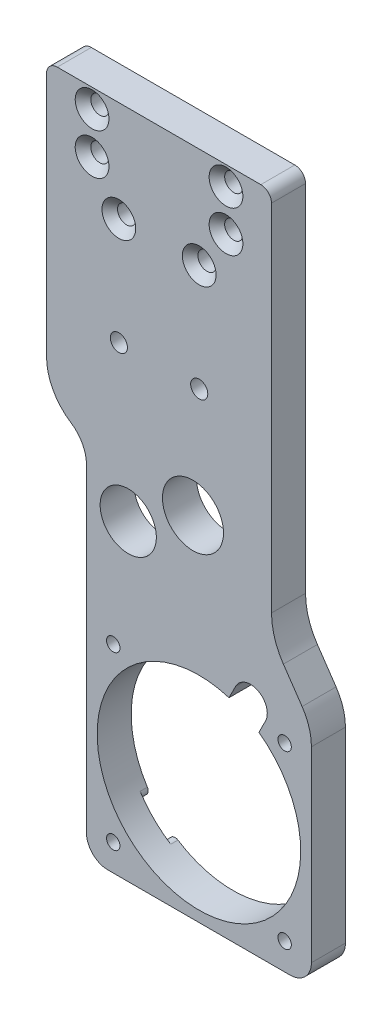
SolidWorks part; units mm, degrees
note: '?' marks a value the reader was unsure of.
ref_plane "Top Plane" through (0, 0, 0) normal (0, 0, 1) x (1, 0, 0)
ref_plane "Front Plane" through (0, 0, 0) normal (0, 1, 0) x (1, 0, 0)
ref_plane "Right Plane" through (0, 0, 0) normal (1, 0, 0) x (0, 0, -1)
sketch "HotendMountingPlateLayout" plane through (0, 0, 0) normal (0, 0, 1) x (1, 0, 0)
  line B0 (-21, 13.5) -> (21, 13.5)
  line B1 (-21, 13.5) -> (-21, -31.3716)
  line B2 (-21, -31.3716) -> (21, -31.3716)
  line B3 (21, 13.5) -> (21, -31.3716)
  line B4 (-21, 13.5) -> (21, -31.3716) construction
  line B5 (-21, -31.3716) -> (21, 13.5) construction
  line B6 (-21, -44.6284) -> (21, -44.6284)
  line B7 (-21, -44.6284) -> (-21, -31.3716)
  line B8 (-21, -31.3716) -> (21, -31.3716)
  line B9 (21, -44.6284) -> (21, -31.3716)
  line B10 (-21, -44.6284) -> (21, -31.3716) construction
  line B11 (-21, -31.3716) -> (21, -44.6284) construction
  line B12 (-13.55, -96.2852) -> (28.45, -96.2852)
  line B13 (-13.55, -96.2852) -> (-13.55, -54.2852)
  line B14 (-13.55, -54.2852) -> (28.45, -54.2852)
  line B15 (28.45, -96.2852) -> (28.45, -54.2852)
  line B16 (-13.55, -96.2852) -> (28.45, -54.2852) construction
  line B17 (-13.55, -54.2852) -> (28.45, -96.2852) construction
  circle B18 centre (-5.75, -38) radius 6.8
  circle B19 centre (0, -38) radius 6
  circle B20 centre (-5.75, -38) radius 0.875
  line B21 (-17.77, -13.5) -> (17.77, -13.5)
  line B22 (-17.77, -13.5) -> (-17.77, 13.5)
  line B23 (-17.77, 13.5) -> (17.77, 13.5)
  line B24 (17.77, -13.5) -> (17.77, 13.5)
  line B25 (-17.77, -13.5) -> (17.77, 13.5) construction
  line B26 (-17.77, 13.5) -> (17.77, -13.5) construction
  line B27 (-12.55, -95.2852) -> (27.45, -95.2852) construction
  line B28 (-12.55, -95.2852) -> (-12.55, -55.2852) construction
  line B29 (-12.55, -55.2852) -> (27.45, -55.2852) construction
  line B30 (27.45, -95.2852) -> (27.45, -55.2852) construction
  line B31 (-12.55, -95.2852) -> (27.45, -55.2852) construction
  line B32 (-12.55, -55.2852) -> (27.45, -95.2852) construction
sketch_block_instance "Block2-1"
sketch_block "Block2" parameters "D3"=12, "D4"=1.75, "D5"=13.6, "D1"=42, "D2"=42, "D6"=20, "D7"=31.7831, "D8"=17.4894, "D9"=26.5358, "D10"=6.875
sketch "Sketch43" plane through (0, 0, 0) normal (0, 0, 1) x (1, 0, 0)
  line L0 (-12.5, 17.55) -> (12.5, 17.55) construction
  line L1 (-12.5, 17.55) -> (-12.5, 25.24) construction
  line L2 (-12.5, 25.24) -> (12.5, 25.24) construction
  line L3 (12.5, 17.55) -> (12.5, 25.24) construction
  line L4 (-12.5, 17.55) -> (12.5, 25.24) construction
  line L5 (-12.5, 25.24) -> (12.5, 17.55) construction
  line L7 (-9.3246, 17.55) -> (-10.9123, 20.3)
  line L8 (-10.9123, 20.3) -> (-14.0877, 20.3)
  line L9 (-14.0877, 20.3) -> (-15.6754, 17.55)
  line L10 (-15.6754, 17.55) -> (-14.0877, 14.8)
  line L11 (-14.0877, 14.8) -> (-10.9123, 14.8)
  line L12 (-10.9123, 14.8) -> (-9.3246, 17.55)
  circle A0 centre (-12.5, 17.55) radius 2.75 construction
  point P0 (0, 21.395)
  dimension "D3" = 5.5
  dimension "D1" = 7.69
  dimension "D2" = 25
  dimension "D4" = 17.55
sketch "Sketch1" plane through (0, 0, 0) normal (0, 0, 1) x (1, 0, 0)
  line L0 (28.45, -96.2852) -> (-13.55, -96.2852)
  line L1 (-21, -41.3815) -> (-21, -54.2852)
  line L2 (-13.55, -96.2852) -> (-13.55, -54.2852)
  line L3 (-13.55, -54.2852) -> (-21, -41.3815) construction
  line L4 (-21, -41.3815) -> (-21, 28.8)
  line L5 (-21, 28.8) -> (21, 28.8)
  line L6 (21, 28.8) -> (21, -41.3815)
  line L7 (-21, -54.2852) -> (-13.55, -54.2852)
  line L8 (21, -41.3815) -> (28.45, -54.2852) construction
  line L9 (28.45, -54.2852) -> (28.45, -96.2852)
  line L10 (21, -41.3815) -> (28.45, -41.3815)
  line L11 (28.45, -41.3815) -> (28.45, -54.2852)
  line L12 (-12.5, 25.24) -> (12.5, 25.24) construction
  line L13 (21, -44.6284) -> (21, -31.3716) construction
  line L14 (-13.55, -54.2852) -> (28.45, -54.2852) construction
  line L15 (-13.55, -54.2852) -> (28.45, -96.2852) construction
  dimension "D1" = 30
  dimension "D2" = 3.56
  dimension "D3" = 42
extrude "Boss-Extrude1" add sketch "Sketch1" along normal blind 6.35
sketch "Sketch2" plane through (0, 0, 6.35) normal (0, 0, 1) x (1, 0, 0)
  circle A0 centre (7.45, -75.2852) radius 19
  dimension "D1" = 38
extrude "Cut-Extrude1" cut sketch "Sketch2" against normal through all
sketch "FanScrewLayout" plane through (0, 0, 6.35) normal (0, 0, 1) x (1, 0, 0)
  line L1 (-8.55, -91.2852) -> (23.45, -91.2852) construction
  line L2 (-8.55, -91.2852) -> (-8.55, -59.2852) construction
  line L3 (-8.55, -59.2852) -> (23.45, -59.2852) construction
  line L4 (23.45, -91.2852) -> (23.45, -59.2852) construction
  line L5 (-8.55, -91.2852) -> (23.45, -59.2852) construction
  line L6 (-8.55, -59.2852) -> (23.45, -91.2852) construction
  point P0 (7.45, -75.2852)
  dimension "D1" = 32
hole_wizard "M3x0.5 Tapped Hole1" positions "Sketch5" profile "Sketch4" tap size "M3x0.5" standard "ANSI Metric" end condition through all
sketch "Sketch5" plane through (0, 0, 6.35) normal (0, 0, 1) x (1, 0, 0)
  point P0 (-8.55, -59.2852)
  point P2 (23.45, -91.2852)
  point P5 (-8.55, -91.2852)
  point P11 (23.45, -59.2852)
sketch "Sketch4" plane through (-8.55, -59.2852, 6.35) normal (1, 0, 0) x (0, -1, 0)
  line L0 (0, 0) -> (0, 6.35)
  line L1 (0, 6.35) -> (1.25, 6.35)
  line L2 (1.25, 6.35) -> (1.25, 0)
  line L5 (1.25, 0) -> (0, 0)
  line L11 (0, -6.35) -> (0, 107.95) construction
  dimension "Thru Tap Drill Dia." = 2.5
  dimension "Thru Tap Drill Depth" = 6.35
cosmetic thread "Hole Thread3" parameters "D2"=3
cosmetic thread "Hole Thread4" [suppressed] parameters "D2"=3
cosmetic thread "Hole Thread5" [suppressed] parameters "D2"=3
cosmetic thread "Hole Thread8" parameters "D2"=3
sketch "CarriageScrewLayout" plane through (0, 0, 6.35) normal (0, 0, 1) x (1, 0, 0)
  line L1 (-7.5, -10) -> (7.5, -10) construction
  line L2 (-7.5, -10) -> (-7.5, 10) construction
  line L3 (-7.5, 10) -> (7.5, 10) construction
  line L4 (7.5, -10) -> (7.5, 10) construction
  line L5 (-7.5, -10) -> (7.5, 10) construction
  line L6 (-7.5, 10) -> (7.5, -10) construction
  point P0 (0, 0)
  dimension "D1" = 20
  dimension "D2" = 15
hole_wizard "Ø3.2 (3.2) Diameter Hole2" positions "Sketch12" profile "Sketch11" hole size "Ø3.2" standard "ANSI Metric"
sketch "Sketch12" plane through (0, 0, 6.35) normal (0, 0, 1) x (1, 0, 0)
  point P0 (7.5, -10)
  point P3 (-7.5, -10)
sketch "Sketch11" plane through (7.5, -10, 6.35) normal (1, 0, 0) x (0, -1, 0)
  line L0 (0, 0) -> (0, 9.53)
  line L1 (0, 9.53) -> (1.6, 9.53)
  line L2 (1.6, 9.53) -> (1.6, 0)
  line L5 (1.6, 0) -> (0, 0)
  line L10 (0, 9.53) -> (-1.6, 9.53) construction
  line L11 (0, -6.35) -> (0, 107.95) construction
  dimension "Hole Dia." = 3.2
  dimension "Hole Depth" = 9.53
  dimension "Drill Angle" = 180
hole_wizard "CSK for M3 Flat Head Machine Screw1" positions "Sketch14" profile "Sketch13" countersink size "M3" standard "ANSI Metric" end condition through all
sketch "Sketch14" plane through (0, 0, 6.35) normal (0, 0, 1) x (1, 0, 0)
  point P0 (-7.5, 10)
  point P3 (7.5, 10)
sketch "Sketch13" plane through (-7.5, 10, 6.35) normal (1, 0, 0) x (0, -1, 0)
  line L0 (0, 0) -> (0, 6.35)
  line L1 (0, 6.35) -> (1.7, 6.35)
  line L2 (1.7, 6.35) -> (1.7, 1.45)
  line L3 (1.7, 1.45) -> (3.15, 0)
  line L5 (3.15, 0) -> (0, 0)
  line L6 (-1.7, 1.45) -> (-3.15, 0) construction
  line L11 (0, -6.35) -> (0, 107.95) construction
  dimension "Thru Hole Dia." = 3.4
  dimension "Thru Hole Depth" = 6.35
  dimension "Near C'Sink Dia." = 6.3
  dimension "Near C'Sink Angle" = 90
hole_wizard "CSK for M3 Flat Head Machine Screw2" positions "Sketch17" profile "Sketch16" countersink size "M3" standard "ANSI Metric" end condition through all
sketch "Sketch17" plane through (0, 0, 6.35) normal (0, 0, 1) x (1, 0, 0)
  point P0 (-12.5, 17.55)
  point P3 (-12.5, 25.24)
  point P6 (12.5, 17.55)
  point P9 (12.5, 25.24)
sketch "Sketch16" plane through (-12.5, 17.55, 6.35) normal (1, 0, 0) x (0, -1, 0)
  line L0 (0, 0) -> (0, 6.35)
  line L1 (0, 6.35) -> (1.7, 6.35)
  line L2 (1.7, 6.35) -> (1.7, 1.45)
  line L3 (1.7, 1.45) -> (3.15, 0)
  line L5 (3.15, 0) -> (0, 0)
  line L6 (-1.7, 1.45) -> (-3.15, 0) construction
  line L11 (0, -6.35) -> (0, 107.95) construction
  dimension "Thru Hole Dia." = 3.4
  dimension "Thru Hole Depth" = 6.35
  dimension "Near C'Sink Dia." = 6.3
  dimension "Near C'Sink Angle" = 90
ref_plane "FingerGuardMount" through (0, 0, 1.35) normal (0, 0, 1) x (1, 0, 0)
hole_wizard "M12x1.5 Tapped Hole4" positions "Sketch19" profile "Sketch18" tap size "M12x1.5" standard "ANSI Metric" end condition through all
sketch "Sketch19" plane through (0, 0, 6.35) normal (0, 0, 1) x (1, 0, 0)
  point P0 (-5.75, -38)
sketch "Sketch18" plane through (-5.75, -38, 6.35) normal (1, 0, 0) x (0, -1, 0)
  line L0 (0, 0) -> (0, 6.35)
  line L1 (0, 6.35) -> (5.25, 6.35)
  line L2 (5.25, 6.35) -> (5.25, 0)
  line L5 (5.25, 0) -> (0, 0)
  line L11 (0, -6.35) -> (0, 107.95) construction
  dimension "Thru Tap Drill Dia." = 10.5
  dimension "Thru Tap Drill Depth" = 6.35
cosmetic thread "Hole Thread9" parameters "D2"=12
sketch "Sketch42" plane through (0, 0, 6.35) normal (0, 0, 1) x (1, 0, 0)
  line L0 (-1.2034, -35.375) -> (1.3947, -33.875) construction
  line L1 (-1.2034, -35.375) -> (4.5212, -35.375) construction
  circle A0 centre (6.3311, -31.025) radius 5.7
  circle A1 centre (-5.75, -38) radius 5.25 construction
  dimension "D1" = 11.4
  dimension "D2" = 30
  dimension "D3" = 3
extrude "Cut-Extrude11" cut sketch "Sketch42" against normal through all
sketch "Sketch20" plane through (0, 0, 6.35) normal (0, 0, 1) x (1, 0, 0)
  line L1 (-5.75, -37.5) -> (-29.6805, -37.5)
  line L2 (-5.75, -37.5) -> (-5.75, -38.5)
  line L3 (-5.75, -38.5) -> (-29.6805, -38.5)
  line L4 (-29.6805, -37.5) -> (-29.6805, -38.5)
  dimension "D1" = 1
extrude "Cut-Extrude2" [suppressed] cut sketch "Sketch20" against normal through all
hole_wizard "M3x0.5 Tapped Hole2" [suppressed] positions "Sketch27" profile "Sketch28" tap size "M3x0.5" standard "ANSI Metric"
sketch "Sketch27" [suppressed] plane through (0, -37.5, 0) normal (0, -1, 0) x (-1, 0, 0)
  point P0 (17.275, -3.175)
sketch "Sketch28" plane through (-17.275, -37.5, 3.175) normal (1, 0, 0) x (0, 0, -1)
  line L0 (0, 0) -> (0, 8.2511)
  line L1 (0, 8.2511) -> (1.25, 7.5)
  line L2 (1.25, 7.5) -> (1.25, 0)
  line L5 (1.25, 0) -> (0, 0)
  line L10 (0, 8.2511) -> (-1.25, 7.5) construction
  line L11 (0, -6.35) -> (0, 107.95) construction
  dimension "Tap Drill Dia." = 2.5
  dimension "Tap Drill Depth" = 7.5
  dimension "Drill Angle" = 118
cosmetic thread "Hole Thread6" [suppressed] parameters "D1"=6, "D2"=3
move or copy body "Body-Move/Copy1" [suppressed] bodies to move or copy 113 copy yes number of copies 1 translate (42, 0, 0)
sketch "Sketch22" [suppressed] plane through (0, 0, 6.35) normal (0, 0, 1) x (1, 0, 0)
  line L0 (21, -43.9) -> (28.45, -43.9) construction
  line L1 (21.725, -43.9) -> (27.725, -43.9)
  line L2 (21.725, -43.9) -> (21.725, -46.9)
  line L3 (21.725, -46.9) -> (27.725, -46.9)
  line L4 (27.725, -43.9) -> (27.725, -46.9)
  line L7 (40.15, -43.9) -> (21, -43.9) construction
  point P6 (24.725, -46.9)
  point P7 (24.725, -43.9)
  dimension "D1" = 3
  dimension "D2" = 6
sketch "Sketch29" [suppressed] plane through (0, 0, 6.35) normal (0, 0, 1) x (1, 0, 0)
  line L0 (21, -41.3815) -> (21, -46.1038)
  line L1 (21, -46.1038) -> (28.45, -54.2852)
  line L2 (28.45, -54.2852) -> (28.45, -41.3815)
  line L3 (21, -43.9) -> (21, -38.5) construction
  line L4 (21, -41.3815) -> (28.45, -41.3815)
extrude "Cut-Extrude5" [suppressed] cut sketch "Sketch29" against normal through all
delete or keep bodies "Body-Delete1" [suppressed] type delete bodies bodies 114
sketch "Sketch31" plane through (0, 0, 6.35) normal (0, 0, 1) x (1, 0, 0)
  line L0 (-13.55, -32.75) -> (-13.55, -54.2852)
  line L1 (-19.9, -26.4) -> (-21, -26.4)
  line L2 (-13.55, -96.2852) -> (-13.55, -54.2852) construction
  line L4 (-21, -54.2852) -> (-21, 28.8) construction
  line L5 (-21, -26.4) -> (-21, -54.2852)
  line L6 (-21, -54.2852) -> (-13.55, -54.2852)
  circle A0 centre (-5.75, -38) radius 5.25 construction
  arc A1 (-13.55, -32.75) -> (-19.9, -26.4) centre (-19.9, -32.75) ccw
  point P5 (-5.75, -32.75)
  point P6 (-11, -38)
  dimension "D2" = 12.7
extrude "Cut-Extrude6" cut sketch "Sketch31" against normal through all
sketch "Sketch32" plane through (0, 0, 6.35) normal (0, 0, 1) x (1, 0, 0)
  line L0 (-13.55, -54.2852) -> (-5.75, -54.2852)
  line L1 (-4.1625, -52.6977) -> (-4.1625, -38)
  line L2 (-4.1625, -38) -> (-7.3375, -38)
  line L3 (-7.3375, -38) -> (-7.3375, -51.1102)
  line L4 (-7.3375, -51.1102) -> (-13.55, -51.1102)
  line L5 (-13.55, -51.1102) -> (-13.55, -54.2852)
  arc A0 (-5.75, -54.2852) -> (-4.1625, -52.6977) centre (-5.75, -52.6977) ccw
  circle A1 centre (-5.75, -52.6977) radius 1.5875 construction
  dimension "D1" = 3.175
sketch "Sketch40" plane through (0, 0, 1.35) normal (0, 0, 1) x (1, 0, 0)
  circle A0 centre (-8.55, -59.2852) radius 4.25
  dimension "D1" = 8.5
extrude "Cut-Extrude9" cut sketch "Sketch40" against normal through all
fillet "Fillet7" radius 1 2 edges at (-7.3413, -63.3597, 0.675) (-4.4755, -60.4939, 0.675)
ref_axis "Axis1" through (7.45, -75.2852, 0) along (0, 0, 1)?
pattern_circular "CirPattern1" count 4 over 360 about axis through (7.45, -75.2852, 0) along (0, 0, 1) of "Cut-Extrude9", "Fillet7"
sketch "Sketch41" plane through (0, 0, 1.35) normal (0, 0, 1) x (1, 0, 0)
  line L0 (-4.3526, -58.6185) -> (-5.3226, -52.5127)
  line L1 (-5.3226, -52.5127) -> (-15.3226, -52.5127)
  line L2 (-15.3226, -52.5127) -> (-15.3226, -62.5127)
  line L3 (-15.3226, -62.5127) -> (-9.2168, -63.4826)
  line L4 (-9.2168, -63.4826) -> (-4.3526, -58.6185)
  circle A0 centre (-8.55, -59.2852) radius 4.25 construction
  dimension "D1" = 10
extrude "Cut-Extrude10" cut sketch "Sketch41" against normal through all
move or copy body "Body-Move/Copy2" bodies to move or copy 124 copy yes number of copies 1 translate (42, 0, 0)
sketch "Sketch37" plane through (0, 0, 6.35) normal (0, 0, 1) x (1, 0, 0)
  line L0 (21, -43.3815) -> (21, -41.3815)
  line L1 (28.45, -41.3815) -> (28.45, -54.2852)
  line L2 (28.45, -54.2852) -> (21, -43.3815)
  line L4 (21, 28.8) -> (21, -41.3815) construction
  line L5 (21, -41.3815) -> (28.45, -41.3815) construction
  line L6 (21, -41.3815) -> (28.45, -41.3815)
  dimension "D1" = 2
extrude "Cut-Extrude8" cut sketch "Sketch37" against normal through all
delete or keep bodies "Body-Delete2" type delete bodies bodies 120
fillet "Fillet3" radius 12.7 1 edges at (21, -43.3815, 3.175)
fillet "Fillet1" radius 4 2 edges at (-13.55, -96.2852, 3.175) (28.45, -96.2852, 3.175)
fillet "Fillet2" [suppressed] radius 10
fillet "Fillet4" radius 2 2 edges at (-21, 28.8, 3.175) (21, 28.8, 3.175)
fillet "Fillet5" radius 10 1 edges at (-21, -26.4, 3.175)
fillet "Fillet6" radius 10 1 edges at (28.45, -54.2852, 3.175)
sketch "Sketch44" [suppressed] plane through (0, 0, 0) normal (1, 0, 0) x (0, 0, -1)
  line L0 (0, 47.8) -> (0, -39.4571) construction
  line L1 (0, 35) -> (-1, 35)
  line L2 (0, 35) -> (0, 18.7)
  line L3 (0, 18.7) -> (-1, 18.7)
  line L4 (-1, 35) -> (-1, 18.7)
  dimension "D1" = 1
  dimension "D2" = 16.3
  dimension "D3" = 14.8
extrude "Cut-Extrude12" [suppressed] cut sketch "Sketch44" against normal through all and the other way through all
sketch "Sketch47" plane through (0, 0, 0) normal (0, 0, -1) x (-1, 0, 0)
  text T0 "2516-2_R4"
extrude "Cut-Extrude15" [suppressed] cut sketch "Sketch47" against normal blind 0.2
sketch "Sketch48" plane through (0, 0, 0) normal (0, 0, -1) x (-1, 0, 0)
  text T0 "2516-1_R3.1\r\n"
extrude "Cut-Extrude16" cut sketch "Sketch48" against normal blind 0.2
sketch "Sketch49" plane through (0, 0, 6.35) normal (0, 0, 1) x (1, 0, 0)
  line L0 (17.0817, -56.0898) -> (14.8605, -60.5165) construction
  line L1 (19.8748, -57.4913) -> (17.6536, -61.918)
  line L2 (14.2886, -54.6883) -> (12.0674, -59.115)
  line L3 (22.0199, -58.5677) -> (19.8748, -57.4913) construction
  arc A0 (19.8748, -57.4913) -> (14.2886, -54.6883) centre (17.0817, -56.0898) ccw
  arc A1 (12.0674, -59.115) -> (17.6536, -61.918) centre (14.8605, -60.5165) ccw
  circle A2 centre (7.45, -75.2852) radius 19 construction
  circle A3 centre (23.45, -59.2852) radius 1.6 construction
  point P2 (15.9711, -58.3032)
  dimension "D1" = 6.25
  dimension "D2" = 3.2
  dimension "D3" = 2.4
extrude "Cut-Extrude17" cut sketch "Sketch49" against normal through all
ref_plane "Plane4" [suppressed] through (15.235, 0, 0) normal (1, 0, 0) x (0, 0, -1)
ref_plane "Plane3" [suppressed] through (0, -38.0357, 0) normal (0, 1, 0) x (1, 0, 0)
sketch "Sketch50" [suppressed] plane through (0, 0, 6.35) normal (0, 0, 1) x (1, 0, 0)
  line L0 (39.235, -44.7857) -> (39.235, -38.0357)
  line L1 (39.235, -38.0357) -> (9.235, -38.0357)
  line L2 (9.235, -38.0357) -> (9.235, -41.2857)
  line L3 (12.735, -44.7857) -> (39.235, -44.7857)
  line L6 (55, -38.0357) -> (-55, -38.0357) construction
  arc A1 (9.235, -41.2857) -> (12.735, -44.7857) centre (12.735, -41.2857) ccw
  dimension "D3" = 7
  dimension "D1" = 0.25
  dimension "D2" = 0.25
  dimension "D4" = 30
extrude "Cut-Extrude18" [suppressed] cut sketch "Sketch50" against normal through all
hole_wizard "M3 Clearance Hole3" [suppressed] positions "Sketch52" profile "Sketch51" hole size "M3" standard "ANSI Metric"
sketch "Sketch52" plane through (0, 0, 0) normal (0, 0, -1) x (-1, 0, 0)
  circle A0 centre (-10.4553, -48.5036) radius 4
  point P0 (-10.4553, -48.5036)
  dimension "D1" = 8
sketch "Sketch51" plane through (10.4553, -48.5036, 0) normal (1, 0, 0) x (0, 1, 0)
  line L0 (0, 0) -> (0, 6.35)
  line L1 (0, 6.35) -> (1.6, 6.35)
  line L2 (1.6, 6.35) -> (1.6, 0)
  line L5 (1.6, 0) -> (0, 0)
  line L11 (0, -6.35) -> (0, 107.95) construction
  dimension "Thru Hole Dia." = 3.2
  dimension "Thru Hole Depth" = 6.35
mirror "Mirror1" [suppressed] about plane through (0, -38.0357, 0) normal (0, 1, 0)
